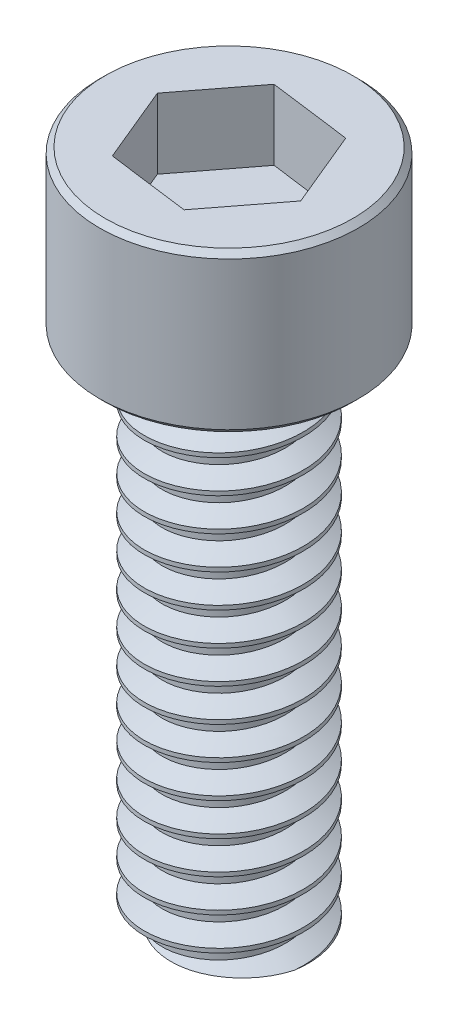
SolidWorks part; units mm, degrees
ref_plane "Front Plane" through (0, 0, 0) normal (0, 0, 1) x (1, 0, 0)
ref_plane "Top Plane" through (0, 0, 0) normal (0, 1, 0) x (1, 0, 0)
ref_plane "Right Plane" through (0, 0, 0) normal (1, 0, 0) x (0, 0, -1)
sketch "Sketch1" plane through (0, 0, 0) normal (0, 1, 0) x (1, 0, 0)
  circle A0 centre (0, 0) radius 1.778
  dimension "D1" = 3.556
extrude "Boss-Extrude1" add sketch "Sketch1" along normal blind 2.1844
chamfer "Chamfer1" distance 0.0762 angle 45 2 edges at (0, 0, 1.778) (0, 2.1844, 1.778)
sketch "Sketch2" plane through (0, 2.1844, 0) normal (0, 1, 0) x (1, 0, 0)
  line L1 (-0.438, 1.0567) -> (-1.1341, 0.149)
  line L2 (-1.1341, 0.149) -> (-0.6961, -0.9076)
  line L3 (-0.6961, -0.9076) -> (0.438, -1.0567)
  line L4 (0.438, -1.0567) -> (1.1341, -0.149)
  line L5 (1.1341, -0.149) -> (0.6961, 0.9076)
  line L6 (0.6961, 0.9076) -> (-0.438, 1.0567)
  circle A0 centre (0, 0) radius 0.9906 construction
extrude "Cut-Extrude1" cut sketch "Sketch2" against normal blind 0.9652
sketch "Sketch3" plane through (0, 0, 0) normal (0, -1, 0) x (1, 0, 0)
  circle A0 centre (0, 0) radius 1.0922
  dimension "D1" = 2.1844
extrude "Boss-Extrude2" add sketch "Sketch3" along normal blind 6.985
thread "Thread1" pitch 0.4536 method cut profile "Thread Profile1" start angle 0, offset 0, length 12.7, pitch 0.4536, diameter 2.1844
ref_plane "Plane1" through (-1.0922, 0, 0) normal (0, 0, 1) x (-1, 0, 0)
sketch "Thread Profile1" plane through (-1.0922, 0, 0) normal (0, 0, 1) x (-1, 0, 0)
  line L0 (0, 0) -> (0, 0.4536) construction
  line L11 (0, 0) -> (0, 0.3969)
  line L12 (0, 0.3969) -> (-0.2455, 0.2551)
  line L13 (-0.2455, 0.2551) -> (-0.2455, 0.1417)
  line L15 (-0.2455, 0.1417) -> (0, 0)
  line L17 (-0.2455, 0.1984) -> (0, 0.1984) construction
  point P2 (0, 0)
  dimension "Pitch" = 0.4536
  dimension "Profile_Angle" = 60
  dimension "Profile_Land" = 0.1134
  dimension "Profile_Height" = 0.2455
